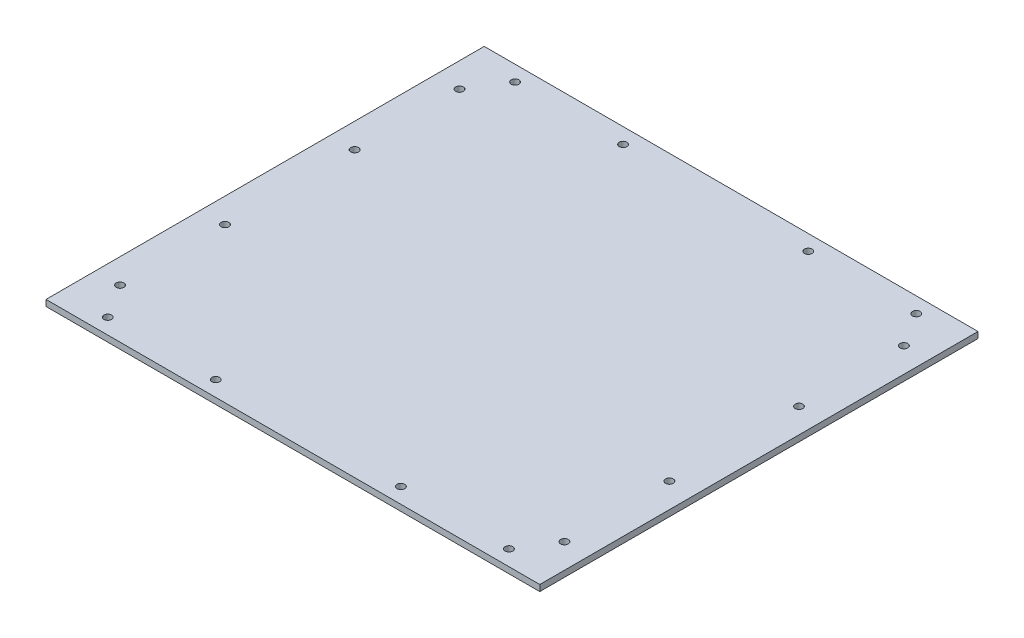
SolidWorks part; units mm, degrees
ref_plane "Front Plane" through (0, 0, 0) normal (0, 0, 1) x (1, 0, 0)
ref_plane "Top Plane" through (0, 0, 0) normal (0, 1, 0) x (1, 0, 0)
ref_plane "Right Plane" through (0, 0, 0) normal (1, 0, 0) x (0, 0, -1)
sketch "Sketch1" plane through (0, 0, 0) normal (0, 1, 0) x (1, 0, 0)
  line L1 (-45, 32) -> (115, 32)
  line L2 (-45, 32) -> (-45, -110)
  line L3 (-45, -110) -> (115, -110)
  line L4 (115, 32) -> (115, -110)
  dimension "D1" = 160
  dimension "D2" = 142
  dimension "D3" = 45
  dimension "D4" = 32
sketch "Sketch2" plane through (0, 0, 0) normal (0, 1, 0) x (1, 0, 0)
  line L4 (115, 32) -> (-45, 32)
  line L5 (115, -110) -> (115, 32)
  line L6 (-45, -110) -> (115, -110)
  line L7 (-45, 32) -> (-45, -110)
  line L8 (115, 32) -> (-45, 32)
  line L9 (115, -110) -> (115, 32)
  line L10 (-45, -110) -> (115, -110)
  line L11 (-45, 32) -> (-45, -110)
  dimension "D1" = 0
extrude "Boss-Extrude1" add sketch "Sketch2" along normal blind 2
sketch "Sketch5" plane through (0, 0, 0) normal (0, 1, 0) x (1, 0, 0)
  circle A16 centre (-37, -18) radius 1 construction
  circle A17 centre (-37, 16) radius 1 construction
  circle A18 centre (-30, 27) radius 1 construction
  circle A19 centre (5, 27) radius 1 construction
  circle A20 centre (65, 27) radius 1 construction
  circle A21 centre (100, 27) radius 1 construction
  circle A22 centre (107, 16) radius 1 construction
  circle A23 centre (107, -18) radius 1 construction
  circle A24 centre (107, -60) radius 1 construction
  circle A25 centre (107, -94) radius 1 construction
  circle A26 centre (65, -105) radius 1 construction
  circle A27 centre (100, -105) radius 1 construction
  circle A28 centre (5, -105) radius 1 construction
  circle A29 centre (-30, -105) radius 1 construction
  circle A30 centre (-37, -94) radius 1 construction
  circle A31 centre (-37, -60) radius 1 construction
  circle A32 centre (-37, -18) radius 1.25
  circle A33 centre (-37, 16) radius 1.25
  circle A34 centre (-30, 27) radius 1.25
  circle A35 centre (5, 27) radius 1.25
  circle A36 centre (65, 27) radius 1.25
  circle A37 centre (100, 27) radius 1.25
  circle A38 centre (107, 16) radius 1.25
  circle A39 centre (107, -18) radius 1.25
  circle A40 centre (107, -60) radius 1.25
  circle A41 centre (107, -94) radius 1.25
  circle A42 centre (65, -105) radius 1.25
  circle A43 centre (100, -105) radius 1.25
  circle A44 centre (5, -105) radius 1.25
  circle A45 centre (-30, -105) radius 1.25
  circle A46 centre (-37, -94) radius 1.25
  circle A47 centre (-37, -60) radius 1.25
  dimension "D1" = 0.25
extrude "Cut-Extrude2" cut sketch "Sketch5" against normal through all and the other way through all
sketch "Sketch6" plane through (0, 0, 0) normal (0, 1, 0) x (1, 0, 0)
  line L0 (-45, 32) -> (-45, -110) construction
  line L1 (-40, 9) -> (-37, 9)
  line L2 (-40, 9) -> (-40, -11)
  line L3 (-40, -11) -> (-37, -11)
  line L4 (-37, 9) -> (-37, -11)
  line L5 (-40, -29) -> (-37, -29)
  line L6 (-40, -29) -> (-40, -49)
  line L7 (-40, -49) -> (-37, -49)
  line L8 (-37, -29) -> (-37, -49)
  line L9 (-40, -67) -> (-37, -67)
  line L10 (-40, -67) -> (-40, -87)
  line L11 (-40, -87) -> (-37, -87)
  line L12 (-37, -67) -> (-37, -87)
  line L13 (-45, 32) -> (115, 32) construction
  line L14 (-45, -110) -> (115, -110) construction
  line L15 (-40, -11) -> (-40, -29) construction
  line L16 (-40, -67) -> (-40, -49) construction
  line L17 (35, 32) -> (35, 27) construction
  line L18 (107, -67) -> (107, -87)
  line L19 (110, -87) -> (107, -87)
  line L20 (110, -67) -> (110, -87)
  line L21 (110, -67) -> (107, -67)
  line L22 (107, -29) -> (107, -49)
  line L23 (110, -49) -> (107, -49)
  line L24 (110, -29) -> (110, -49)
  line L25 (110, -29) -> (107, -29)
  line L26 (110, -11) -> (107, -11)
  line L27 (110, 9) -> (110, -11)
  line L28 (110, 9) -> (107, 9)
  line L29 (107, 9) -> (107, -11)
  dimension "D1" = 20
  dimension "D2" = 3
  dimension "D3" = 5
  dimension "D4" = 23
  dimension "D5" = 23
  dimension "D6" = 5
extrude "Boss-Extrude2" add sketch "Sketch6" against normal blind 5
sketch "Sketch8" plane through (0, 0, 0) normal (0, 1, 0) x (1, 0, 0)
  line L1 (-30, -54.75) -> (23, -54.75)
  line L2 (-30, -54.75) -> (-30, -4.75)
  line L3 (-30, -4.75) -> (23, -4.75)
  line L4 (23, -54.75) -> (23, -4.75)
sketch "Sketch7" plane through (0, 0, 0) normal (0, 1, 0) x (1, 0, 0)
  line L0 (-37, -1) -> (107, -1)
  line L1 (-37, -11) -> (-37, 9) construction
  line L2 (107, 9) -> (107, -11) construction
  line L4 (-37, -77) -> (107, -77)
  line L5 (-37, -87) -> (-37, -67) construction
  line L7 (107, -67) -> (107, -87) construction
  line L10 (35, -77) -> (35, -1)
extrude "Extrude-Thin1" add sketch "Sketch7" against normal blind 5 thin thin type mid plane wall 3
fillet "Fillet6" radius 3 12 edges at (33.5, -2.5, 2.5) (107, -2.5, 2.5) (36.5, -2.5, 2.5) (-37, -2.5, 2.5) (-37, -2.5, -0.5) (107, -2.5, -0.5) (107, -2.5, 75.5) (107, -2.5, 78.5) (-37, -2.5, 78.5) (-37, -2.5, 75.5) (36.5, -2.5, 75.5) (33.5, -2.5, 75.5)
fillet "Fillet1" radius 5 2 edges at (107, 0, 39) (-37, 0, 39)
fillet "Fillet7" radius 3 28 edges at (-37, 0, 84.25) (107, 0, 84.25) (-37, 0, 69.75) (-37, 0, 8.25) (107, 0, 8.25) (107, 0, 69.75) (-37, 0, -6.25) (107, 0, -6.25) (-36.1213, 0, 79.3787) (106.1213, 0, 79.3787) (-36.1213, 0, 3.3787) (-1.75, 0, 2.5) (-36.1213, 0, 74.6213) (-1.75, 0, 75.5) (32.6213, 0, 74.6213) (33.5, 0, 39) (106.1213, 0, 74.6213) (71.75, 0, 75.5) (37.3787, 0, 74.6213) (36.5, 0, 39) (106.1213, 0, 3.3787) (71.75, 0, 2.5) (-36.1213, 0, -1.3787) (106.1213, 0, -1.3787) (35, 0, 78.5) (32.6213, 0, 3.3787) (37.3787, 0, 3.3787) (35, 0, -0.5)
